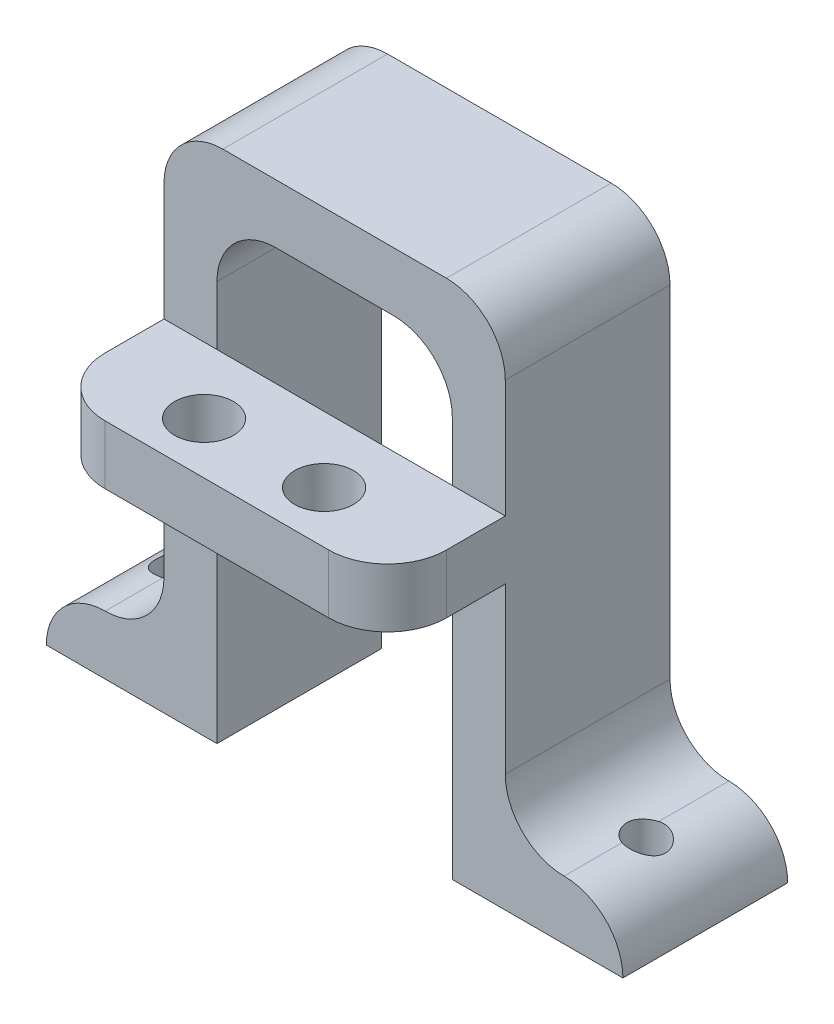
SolidWorks part; units mm, degrees
ref_plane "Front Plane" through (0, 0, 0) normal (0, 0, 1) x (1, 0, 0)
ref_plane "Top Plane" through (0, 0, 0) normal (0, 1, 0) x (1, 0, 0)
ref_plane "Right Plane" through (0, 0, 0) normal (1, 0, 0) x (0, 0, -1)
sketch "Sketch1" plane through (0, 0, 0) normal (0, 0, 1) x (1, 0, 0)
  line L0 (-24.5, 0) -> (-24.5, 5)
  line L1 (7.7, 0) -> (-7.7, 0) construction
  line L2 (-24.5, 5) -> (-14.5, 5)
  line L3 (-14.5, 5) -> (-14.5, 44)
  line L4 (-14.5, 44) -> (14.5, 44)
  line L5 (-24.5, 0) -> (-10, 0)
  line L6 (-10, 0) -> (-10, 39)
  line L7 (-10, 39) -> (10, 39)
  line L8 (0, -16.5) -> (0, 16.5) construction
  line L9 (24.5, 0) -> (10, 0)
  line L10 (24.5, 0) -> (24.5, 5)
  line L11 (24.5, 5) -> (14.5, 5)
  line L12 (10, 0) -> (10, 39)
  line L13 (14.5, 5) -> (14.5, 44)
  point P7 (0, 39)
  point P19 (0, 44)
  dimension "D1" = 20
  dimension "D2" = 5
  dimension "D4" = 5
  dimension "D6" = 39
extrude "Boss-Extrude1" add sketch "Sketch1" along normal blind 14
fillet "Fillet1" radius 5 6 edges at (-14.5, 44, 7) (14.5, 44, 7) (24.5, 5, 7) (-24.5, 5, 7) (14.5, 5, 7) (-14.5, 5, 7)
fillet "Fillet2" radius 5 2 edges at (10, 39, 7) (-10, 39, 7)
sketch "Sketch2" plane through (0, 0, 0) normal (0, 1, 0) x (1, 0, 0)
  line L0 (0, -16.5) -> (0, 16.5) construction
  circle A0 centre (-20, -7.5233) radius 1.636
  circle A1 centre (20, -7.5233) radius 1.636
  dimension "D1" = 40
extrude "Cut-Extrude3" cut sketch "Sketch2" against normal blind 10 and the other way blind 10 contours A0 | A1
sketch "Sketch4" plane through (0, 0, 14) normal (0, 0, 1) x (1, 0, 0)
  line L0 (-14.5, 39) -> (-14.5, 10) construction
  line L1 (9.5, 44) -> (-9.5, 44)
  line L2 (9.5, 44) -> (9.5, 39)
  line L3 (9.5, 39) -> (-9.5, 39)
  line L4 (-9.5, 44) -> (-9.5, 39)
  line L5 (-14.5, 29) -> (14.5, 29)
  line L6 (-14.5, 29) -> (-14.5, 24)
  line L7 (-14.5, 24) -> (14.5, 24)
  line L8 (14.5, 29) -> (14.5, 24)
  line L9 (14.5, 10) -> (14.5, 39) construction
  dimension "D1" = 15
  dimension "D2" = 5
extrude "Boss-Extrude2" add sketch "Sketch4" along normal blind 10 contours L6 L5 L8 L7
sketch "Sketch5" plane through (0, 44, 0) normal (0, 1, 0) x (1, 0, 0)
  circle A0 centre (4.7058, -19.6015) radius 2.5
  circle A1 centre (-5.4774, -19.6181) radius 2.5
  dimension "D1" = 5
  dimension "D2" = 5
extrude "Cut-Extrude4" cut sketch "Sketch5" against normal blind 30
fillet "Fillet3" radius 5 2 edges at (-14.5, 26.5, 24) (14.5, 26.5, 24)
